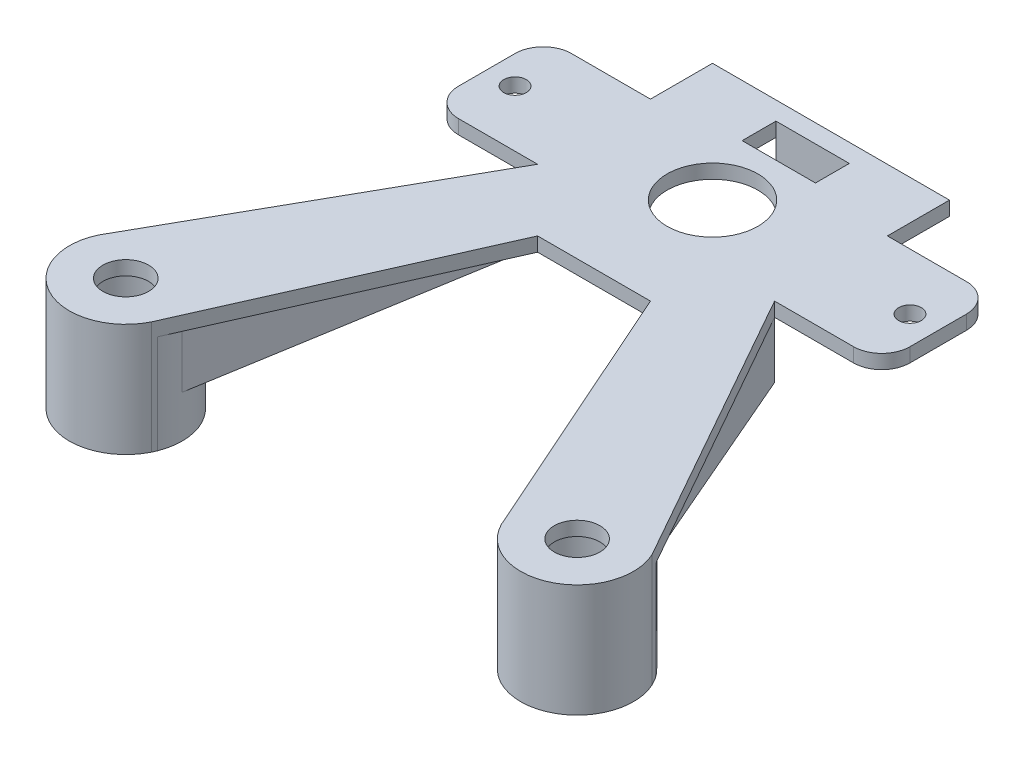
SolidWorks part; units mm, degrees
ref_plane "前视基准面" through (0, 0, 0) normal (0, 0, 1) x (1, 0, 0)
ref_plane "上视基准面" through (0, 0, 0) normal (0, 1, 0) x (1, 0, 0)
ref_plane "右视基准面" through (0, 0, 0) normal (1, 0, 0) x (0, 0, -1)
sketch "草图6" plane through (0, 0, 0) normal (0, 1, 0) x (1, 0, 0)
  line L1 (-21, -21) -> (21, -21)
  line L2 (-21, -21) -> (-21, 21)
  line L3 (-21, 21) -> (21, 21)
  line L4 (21, -21) -> (21, 21)
  line L5 (0, 21) -> (0, -21) construction
  line L6 (-21, 0) -> (21, 0) construction
  circle A0 centre (0, 0) radius 8.05
  point P0 (0, 0)
  dimension "D2" = 16.1
extrude "凸台-拉伸1" add sketch "草图6" along normal blind 2.5
sketch "草图7" plane through (0, 2.5, 0) normal (0, 1, 0) x (1, 0, 0)
  line L2 (21, -10) -> (49.0892, -59.8303)
  line L4 (-10, -21) -> (-31.0355, -68.4315)
  line L5 (-21, -10) -> (-49.0892, -59.8303)
  line L6 (10, -21) -> (31.0355, -68.4315)
  circle A0 centre (-40, -64) radius 10
  circle A1 centre (40, -64) radius 10
  circle A2 centre (-40, -64) radius 4.05
  circle A3 centre (40, -64) radius 4.05
  line M9 (21, -21) -> (21, 21)
  line M11 (-21, 21) -> (-21, -21)
  line M12 (-21, -21) -> (21, -21)
  dimension "D1" = 8.1
  dimension "D2" = 8.1
extrude "凸台-拉伸5" add sketch "草图7" against normal blind 2.5 contours A1 L2 L6 M9 M12 | A0 L4 L5 M12 M11 | A1 A3 | A0 A2 region at (-27.3301, 2.5, 38.6598) region at (27.3301, 2.5, 38.6598) region at (48.4348, 2.5, 59.2453) region at (-31.1252, 2.5, 67.9359)
extrude "凸台-拉伸7" add sketch "草图7<7>" against normal blind 20 contours A1 A3 region at (48.4348, 2.5, 59.2453)
sketch "草图7<7>" plane through (0, 2.5, 0) normal (0, 1, 0) x (1, 0, 0) same geometry as "草图7"
extrude "凸台-拉伸8" add sketch "草图7<8>" against normal blind 20 contours A0 A2 region at (-31.1252, 2.5, 67.9359)
sketch "草图7<8>" plane through (0, 2.5, 0) normal (0, 1, 0) x (1, 0, 0) same geometry as "草图7"
ref_plane "基准面1" through (0, 2.5, 0) normal (0, 1, 0) x (1, 0, 0)
sketch "草图8" plane through (0, 0, 0) normal (0, -1, 0) x (1, 0, 0)
  line L0 (40, 54) -> (21, 10)
  line L1 (30, 64) -> (21, 10)
  line L2 (-30, 64) -> (-21, 10)
  line L3 (-40, 54) -> (-21, 10)
  arc A0 (30.6977, 67.6697) -> (48.2732, 58.3826) centre (40, 64) ccw construction
  arc A1 (30.6977, 67.6697) -> (48.2732, 58.3826) centre (40, 64) ccw construction
  arc A4 (-48.2732, 58.3826) -> (-30.6977, 67.6697) centre (-40, 64) ccw construction
  arc A5 (-48.2732, 58.3826) -> (-30.6977, 67.6697) centre (-40, 64) ccw construction
  arc A6 (-40, 54) -> (-30, 64) centre (-40, 64) ccw
  arc A7 (30, 64) -> (40, 54) centre (40, 64) ccw
extrude "凸台-拉伸9" add sketch "草图8" along normal blind 10
sketch "草图9" plane through (0, -17.5, 0) normal (0, -1, 0) x (1, 0, 0)
  circle A0 centre (-40, 64) radius 7.6
  circle A1 centre (40, 64) radius 7.6
  dimension "D1" = 15.2
  dimension "D2" = 15.2
extrude "切除-拉伸1" cut sketch "草图9" against normal blind 17.5
sketch "草图10" plane through (0, 0, 0) normal (0, -1, 0) x (-1, 0, 0)
  line L0 (-21, 21) -> (21, 21) construction
  line L1 (6.5, 11.75) -> (-6.5, 11.75)
  line L2 (6.5, 11.75) -> (6.5, 17.75)
  line L3 (6.5, 17.75) -> (-6.5, 17.75)
  line L4 (-6.5, 11.75) -> (-6.5, 17.75)
  line L5 (6.5, 11.75) -> (-6.5, 17.75) construction
  line L6 (6.5, 17.75) -> (-6.5, 11.75) construction
  point P0 (0, 14.75)
  dimension "D1" = 13
  dimension "D2" = 6
  dimension "D3" = 3.25
extrude "切除-拉伸2" cut sketch "草图10" against normal blind 17.5
sketch "草图11" plane through (0, 0, 0) normal (0, -1, 0) x (1, 0, 0)
  line L0 (21, -21) -> (-21, -21) construction
  line L1 (-6.5, -17.75) -> (6.5, -17.75)
  line L2 (-6.5, -17.75) -> (-6.5, -21)
  line L3 (-6.5, -21) -> (6.5, -21)
  line L4 (6.5, -17.75) -> (6.5, -21)
extrude "凸台-拉伸10" add sketch "草图11" along normal blind 5
sketch "草图12" plane through (0, 0, -21) normal (0, 0, -1) x (-1, 0, 0)
  line L0 (-6.5, -5) -> (-6.5, 0) construction
  line L1 (6.5, -5) -> (-6.5, -5) construction
  circle A0 centre (-3, -2.52) radius 1.05
  dimension "D1" = 2.1
  dimension "D2" = 3.5
  dimension "D3" = 2.48
extrude "切除-拉伸3" cut sketch "草图12" against normal blind 17.5
sketch "草图13" plane through (0, 0, 0) normal (0, 1, 0) x (1, 0, 0)
  line L1 (40, 10) -> (21, 10)
  line L2 (40, 10) -> (40, -10)
  line L3 (40, -10) -> (21, -10)
  line L4 (21, 10) -> (21, -10)
  line L5 (-21, -10) -> (-40, -10)
  line L6 (-21, -10) -> (-21, 10)
  line L7 (-21, 10) -> (-40, 10)
  line L8 (-40, -10) -> (-40, 10)
extrude "凸台-拉伸11" add sketch "草图13" along normal blind 2.5
sketch "草图14" plane through (0, 2.5, 0) normal (0, 1, 0) x (1, 0, 0)
  circle A0 centre (35, 0) radius 2
  circle A1 centre (-35, 0) radius 2
  dimension "D1" = 4
  dimension "D2" = 4
extrude "切除-拉伸4" cut sketch "草图14" against normal blind 2.5
fillet "圆角1" radius 5 4 edges at (-40, 1.25, -10) (-40, 1.25, 10) (40, 1.25, 10) (40, 1.25, -10)
